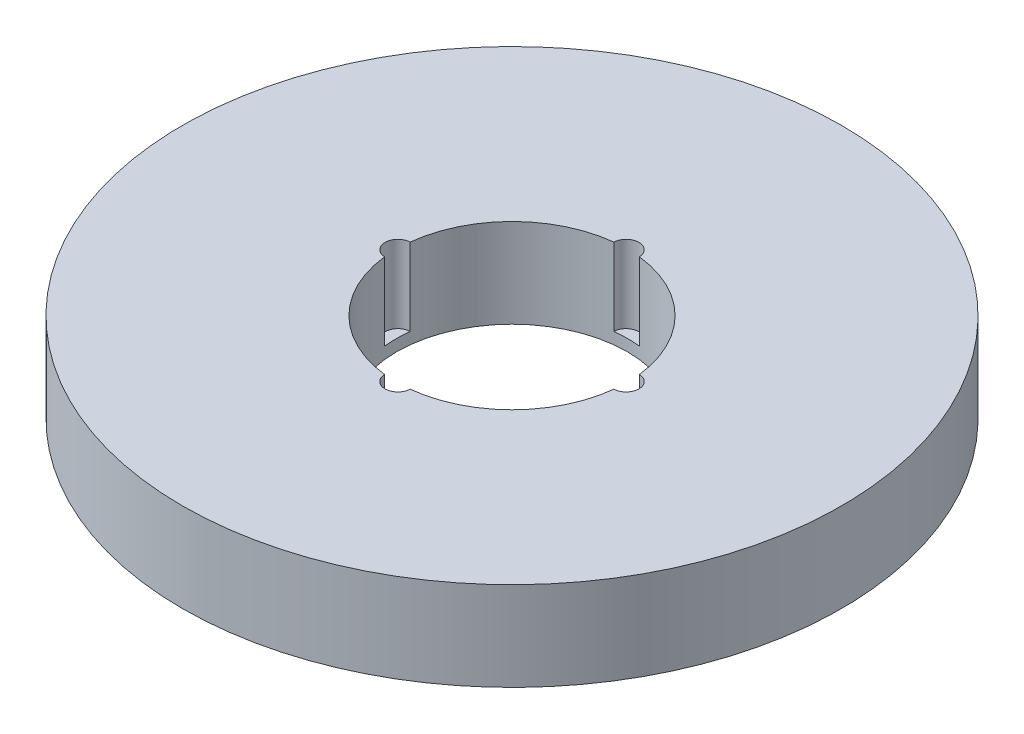
SolidWorks part; units mm, degrees
ref_plane "Front Plane" through (0, 0, 0) normal (0, 0, 1) x (1, 0, 0)
ref_plane "Top Plane" through (0, 0, 0) normal (0, 1, 0) x (1, 0, 0)
ref_plane "Right Plane" through (0, 0, 0) normal (1, 0, 0) x (0, 0, -1)
sketch "Sketch1" plane through (0, 0, 0) normal (0, 1, 0) x (1, 0, 0)
  circle A0 centre (0, 0) radius 100
  dimension "FLANGE_OD" = 200
extrude "Boss-Extrude1" add sketch "Sketch1" along normal blind 27
sketch "Sketch2" plane through (0, 0, 0) normal (0, 1, 0) x (1, 0, 0)
  circle A0 centre (0, 0) radius 35
  dimension "BORE_D" = 70
extrude "Cut-Extrude1" cut sketch "Sketch2" along normal through all
sketch "Sketch3" plane through (0, 27, 0) normal (0, 1, 0) x (1, 0, 0)
  circle A0 centre (0, 0) radius 34.6439 construction
  circle A1 centre (-34.6439, 0) radius 3.8728
  dimension "BOLT_D" = 7.7456
  dimension "BOLT_PCD" = 69.2878
extrude "Cut-Extrude2" cut sketch "Sketch3" against normal blind 23.4821
pattern_circular "CirPattern1" count 4 over 360 about axis through (0, 0, 0) along (0, 1, 0) of "Cut-Extrude2"
